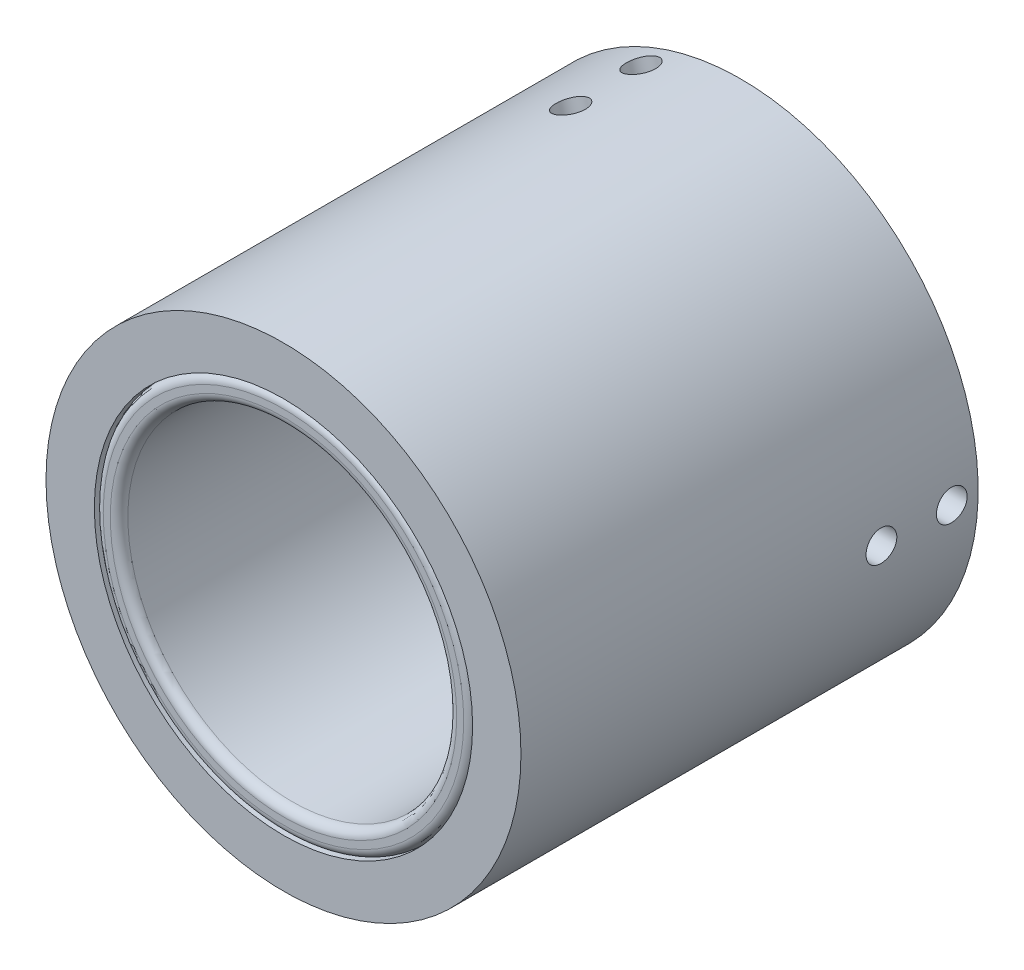
SolidWorks part; units mm, degrees
ref_plane "Plan de face" through (0, 0, 0) normal (0, 0, 1) x (1, 0, 0)
ref_plane "Plan de dessus" through (0, 0, 0) normal (0, 1, 0) x (1, 0, 0)
ref_plane "Plan de droite" through (0, 0, 0) normal (1, 0, 0) x (0, 0, -1)
sketch "Esquisse6" plane through (0, 0, 0) normal (0, 0, 1) x (1, 0, 0)
  line L0 (0, 0) -> (4.4539, 28.1206) construction
  line L1 (0, 0) -> (12.5667, 24.6635) construction
  line L2 (0, 0) -> (19.5026, 19.5026) construction
  line L3 (9.7608, 19.1566) -> (10.8958, 21.3842)
  line L4 (16.9706, 16.9706) -> (15.2028, 15.2028)
  line L5 (19.1566, 9.7608) -> (21.3842, 10.8958)
  line L6 (23.7045, 3.7544) -> (21.2353, 3.3633)
  line L7 (21.2353, -3.3633) -> (23.7045, -3.7544)
  line L8 (21.3842, -10.8958) -> (19.1566, -9.7608)
  line L9 (15.2028, -15.2028) -> (16.9706, -16.9706)
  line L10 (10.8958, -21.3842) -> (9.7608, -19.1566)
  line L11 (3.3633, -21.2353) -> (3.7544, -23.7045)
  line L12 (-3.7544, -23.7045) -> (-3.3633, -21.2353)
  line L13 (-9.7608, -19.1566) -> (-10.8958, -21.3842)
  line L14 (-16.9706, -16.9706) -> (-15.2028, -15.2028)
  line L15 (-19.1566, -9.7608) -> (-21.3842, -10.8958)
  line L16 (-23.7045, -3.7544) -> (-21.2353, -3.3633)
  line L17 (-21.2353, 3.3633) -> (-23.7045, 3.7544)
  line L18 (-21.3842, 10.8958) -> (-19.1566, 9.7608)
  line L19 (-15.2028, 15.2028) -> (-16.9706, 16.9706)
  line L20 (-10.8958, 21.3842) -> (-9.7608, 19.1566)
  line L21 (-3.3633, 21.2353) -> (-3.7544, 23.7045)
  line L22 (3.7544, 23.7045) -> (3.3633, 21.2353)
  line L23 (-10.8958, 21.3842) -> (10.8958, -21.3842) construction
  line L24 (0, 0) -> (0, 33.4225) construction
  line L25 (21.3842, 10.8958) -> (-21.3842, -10.8958) construction
  line L26 (23.7045, 3.7544) -> (-23.7045, -3.7544) construction
  line L27 (23.7045, -3.7544) -> (-23.7045, 3.7544) construction
  line L28 (21.3842, -10.8958) -> (-21.3842, 10.8958) construction
  line L29 (16.9706, -16.9706) -> (-16.9706, 16.9706) construction
  line L30 (3.7544, -23.7045) -> (-3.7544, 23.7045) construction
  line L31 (-3.7544, -23.7045) -> (0, 0) construction
  line L32 (-10.8958, -21.3842) -> (0, 0) construction
  line L33 (-16.9706, -16.9706) -> (0, 0) construction
  circle A0 centre (0, 0) radius 25 construction
  circle A1 centre (0, 0) radius 24 construction
  circle A2 centre (0, 0) radius 21.5 construction
  arc A3 (3.3633, 21.2353) -> (9.7608, 19.1566) centre (0, 0) cw
  arc A4 (10.8958, 21.3842) -> (16.9706, 16.9706) centre (0, 0) cw
  arc A5 (15.2028, 15.2028) -> (19.1566, 9.7608) centre (0, 0) cw
  arc A6 (21.3842, 10.8958) -> (23.7045, 3.7544) centre (0, 0) cw
  arc A7 (21.2353, 3.3633) -> (21.2353, -3.3633) centre (0, 0) cw
  arc A8 (23.7045, -3.7544) -> (21.3842, -10.8958) centre (0, 0) cw
  arc A9 (19.1566, -9.7608) -> (15.2028, -15.2028) centre (0, 0) cw
  arc A10 (16.9706, -16.9706) -> (10.8958, -21.3842) centre (0, 0) cw
  arc A11 (9.7608, -19.1566) -> (3.3633, -21.2353) centre (0, 0) cw
  arc A12 (3.7544, -23.7045) -> (-3.7544, -23.7045) centre (0, 0) cw
  arc A13 (-3.3633, -21.2353) -> (-9.7608, -19.1566) centre (0, 0) cw
  arc A14 (-10.8958, -21.3842) -> (-16.9706, -16.9706) centre (0, 0) cw
  arc A15 (-15.2028, -15.2028) -> (-19.1566, -9.7608) centre (0, 0) cw
  arc A16 (-21.3842, -10.8958) -> (-23.7045, -3.7544) centre (0, 0) cw
  arc A17 (-21.2353, -3.3633) -> (-21.2353, 3.3633) centre (0, 0) cw
  arc A18 (-23.7045, 3.7544) -> (-21.3842, 10.8958) centre (0, 0) cw
  arc A19 (-19.1566, 9.7608) -> (-15.2028, 15.2028) centre (0, 0) cw
  arc A20 (-16.9706, 16.9706) -> (-10.8958, 21.3842) centre (0, 0) cw
  arc A21 (-9.7608, 19.1566) -> (-3.3633, 21.2353) centre (0, 0) cw
  arc A22 (-3.7544, 23.7045) -> (3.7544, 23.7045) centre (0, 0) cw
  circle A23 centre (0, 0) radius 3.025
  circle A24 centre (0, 0) radius 9.025 construction
  circle A25 centre (0, 0) radius 17.5 construction
  point P62 (0, 0)
  dimension "D1" = 50
  dimension "D4" = 2.5
  dimension "D5" = 48
  dimension "D7" = 6.05
  dimension "D9" = 6
  dimension "D10" = 4
  dimension "D2" = 18
  dimension "D3" = 18
  dimension "D8" = 9
  dimension "D6" = 10
extrude "Jante" add sketch "Esquisse6" along normal blind 46 from offset 20
sketch "Esquisse8" plane through (0, 0, 66) normal (0, 0, 1) x (1, 0, 0)
  circle A0 centre (0, 0) radius 21.5
  circle A1 centre (0, 0) radius 3.025
  circle A2 centre (0, 0) radius 3.025 construction
  arc A3 (-15.2028, 15.2028) -> (-19.1566, 9.7608) centre (0, 0) ccw construction
extrude "Boss.-Extru.5" add sketch "Esquisse8" along normal blind 3
sketch "Esquisse9" plane through (0, 0, 20) normal (0, 0, -1) x (-1, 0, 0)
  circle A0 centre (0, 0) radius 21.5
  circle A1 centre (0, 0) radius 3.025
  arc A2 (19.1566, 9.7608) -> (15.2028, 15.2028) centre (0, 0) ccw construction
  circle A3 centre (0, 0) radius 3.025 construction
extrude "Boss.-Extru.6" add sketch "Esquisse9" along normal blind 3
sketch "Esquisse7" plane through (0, 0, 0) normal (0, 0, 1) x (1, 0, 0)
  line L40 (-9.7564, 19.1701) -> (-10.8914, 21.3976)
  line L41 (-16.9847, 16.9706) -> (-15.2169, 15.2028)
  line L42 (-19.161, 9.7742) -> (-21.3885, 10.9092)
  line L43 (-23.716, 3.7461) -> (-21.2467, 3.355)
  line L44 (-21.2467, -3.355) -> (-23.716, -3.7461)
  line L45 (-21.3885, -10.9092) -> (-19.161, -9.7742)
  line L46 (-15.2169, -15.2028) -> (-16.9847, -16.9706)
  line L47 (-10.8914, -21.3976) -> (-9.7564, -19.1701)
  line L48 (-3.3748, -21.2436) -> (-3.7659, -23.7128)
  line L49 (3.7659, -23.7128) -> (3.3748, -21.2436)
  line L50 (9.7564, -19.1701) -> (10.8914, -21.3976)
  line L51 (16.9847, -16.9706) -> (15.2169, -15.2028)
  line L52 (19.161, -9.7742) -> (21.3885, -10.9092)
  line L53 (23.716, -3.7461) -> (21.2467, -3.355)
  line L54 (21.2467, 3.355) -> (23.716, 3.7461)
  line L55 (21.3885, 10.9092) -> (19.161, 9.7742)
  line L56 (15.2169, 15.2028) -> (16.9847, 16.9706)
  line L57 (10.8914, 21.3976) -> (9.7564, 19.1701)
  line L58 (3.3748, 21.2436) -> (3.7659, 23.7128)
  line L59 (-3.7659, 23.7128) -> (-3.3748, 21.2436)
  line L60 (-9.7564, 19.1701) -> (-10.8914, 21.3976)
  line L61 (-16.9847, 16.9706) -> (-15.2169, 15.2028)
  line L62 (-19.161, 9.7742) -> (-21.3885, 10.9092)
  line L63 (-23.716, 3.7461) -> (-21.2467, 3.355)
  line L64 (-21.2467, -3.355) -> (-23.716, -3.7461)
  line L65 (-21.3885, -10.9092) -> (-19.161, -9.7742)
  line L66 (-15.2169, -15.2028) -> (-16.9847, -16.9706)
  line L67 (-10.8914, -21.3976) -> (-9.7564, -19.1701)
  line L68 (-3.3748, -21.2436) -> (-3.7659, -23.7128)
  line L69 (3.7659, -23.7128) -> (3.3748, -21.2436)
  line L70 (9.7564, -19.1701) -> (10.8914, -21.3976)
  line L71 (16.9847, -16.9706) -> (15.2169, -15.2028)
  line L72 (19.161, -9.7742) -> (21.3885, -10.9092)
  line L73 (23.716, -3.7461) -> (21.2467, -3.355)
  line L74 (21.2467, 3.355) -> (23.716, 3.7461)
  line L75 (21.3885, 10.9092) -> (19.161, 9.7742)
  line L76 (15.2169, 15.2028) -> (16.9847, 16.9706)
  line L77 (10.8914, 21.3976) -> (9.7564, 19.1701)
  line L78 (3.3748, 21.2436) -> (3.7659, 23.7128)
  line L79 (-3.7659, 23.7128) -> (-3.3748, 21.2436)
  circle A20 centre (0, 0) radius 27.01
  arc A40 (-3.3748, 21.2436) -> (-9.7564, 19.1701) centre (0, 0) ccw
  arc A41 (-10.8914, 21.3976) -> (-16.9847, 16.9706) centre (0, 0) ccw
  arc A42 (-15.2169, 15.2028) -> (-19.161, 9.7742) centre (0, 0) ccw
  arc A43 (-21.3885, 10.9092) -> (-23.716, 3.7461) centre (0, 0) ccw
  arc A44 (-21.2467, 3.355) -> (-21.2467, -3.355) centre (0, 0) ccw
  arc A45 (-23.716, -3.7461) -> (-21.3885, -10.9092) centre (0, 0) ccw
  arc A46 (-19.161, -9.7742) -> (-15.2169, -15.2028) centre (0, 0) ccw
  arc A47 (-16.9847, -16.9706) -> (-10.8914, -21.3976) centre (0, 0) ccw
  arc A48 (-9.7564, -19.1701) -> (-3.3748, -21.2436) centre (0, 0) ccw
  arc A49 (-3.7659, -23.7128) -> (3.7659, -23.7128) centre (0, 0) ccw
  arc A50 (3.3748, -21.2436) -> (9.7564, -19.1701) centre (0, 0) ccw
  arc A51 (10.8914, -21.3976) -> (16.9847, -16.9706) centre (0, 0) ccw
  arc A52 (15.2169, -15.2028) -> (19.161, -9.7742) centre (0, 0) ccw
  arc A53 (21.3885, -10.9092) -> (23.716, -3.7461) centre (0, 0) ccw
  arc A54 (21.2467, -3.355) -> (21.2467, 3.355) centre (0, 0) ccw
  arc A55 (23.716, 3.7461) -> (21.3885, 10.9092) centre (0, 0) ccw
  arc A56 (19.161, 9.7742) -> (15.2169, 15.2028) centre (0, 0) ccw
  arc A57 (16.9847, 16.9706) -> (10.8914, 21.3976) centre (0, 0) ccw
  arc A58 (9.7564, 19.1701) -> (3.3748, 21.2436) centre (0, 0) ccw
  arc A59 (3.7659, 23.7128) -> (-3.7659, 23.7128) centre (0, 0) ccw
  arc A60 (-3.3748, 21.2436) -> (-9.7564, 19.1701) centre (0, 0) ccw
  arc A61 (-10.8914, 21.3976) -> (-16.9847, 16.9706) centre (0, 0) ccw
  arc A62 (-15.2169, 15.2028) -> (-19.161, 9.7742) centre (0, 0) ccw
  arc A63 (-21.3885, 10.9092) -> (-23.716, 3.7461) centre (0, 0) ccw
  arc A64 (-21.2467, 3.355) -> (-21.2467, -3.355) centre (0, 0) ccw
  arc A65 (-23.716, -3.7461) -> (-21.3885, -10.9092) centre (0, 0) ccw
  arc A66 (-19.161, -9.7742) -> (-15.2169, -15.2028) centre (0, 0) ccw
  arc A67 (-16.9847, -16.9706) -> (-10.8914, -21.3976) centre (0, 0) ccw
  arc A68 (-9.7564, -19.1701) -> (-3.3748, -21.2436) centre (0, 0) ccw
  arc A69 (-3.7659, -23.7128) -> (3.7659, -23.7128) centre (0, 0) ccw
  arc A70 (3.3748, -21.2436) -> (9.7564, -19.1701) centre (0, 0) ccw
  arc A71 (10.8914, -21.3976) -> (16.9847, -16.9706) centre (0, 0) ccw
  arc A72 (15.2169, -15.2028) -> (19.161, -9.7742) centre (0, 0) ccw
  arc A73 (21.3885, -10.9092) -> (23.716, -3.7461) centre (0, 0) ccw
  arc A74 (21.2467, -3.355) -> (21.2467, 3.355) centre (0, 0) ccw
  arc A75 (23.716, 3.7461) -> (21.3885, 10.9092) centre (0, 0) ccw
  arc A76 (19.161, 9.7742) -> (15.2169, 15.2028) centre (0, 0) ccw
  arc A77 (16.9847, 16.9706) -> (10.8914, 21.3976) centre (0, 0) ccw
  arc A78 (9.7564, 19.1701) -> (3.3748, 21.2436) centre (0, 0) ccw
  arc A79 (3.7659, 23.7128) -> (-3.7659, 23.7128) centre (0, 0) ccw
  dimension "D2" = 3
  dimension "D1" = 0.01
extrude "Pneu" add sketch "Esquisse7" along normal up to surface (66 mm away) from offset 20 separate body up to face at (-13.2898, 18.2918, 66)
sketch "Esquisse10" plane through (0, 0, 66) normal (0, 0, 1) x (1, 0, 0)
  circle A1 centre (0, 0) radius 27.01
  circle A3 centre (0, 0) radius 21.51
  circle A4 centre (0, 0) radius 27.01 construction
  arc A5 (-9.7564, -19.1701) -> (-3.3748, -21.2436) centre (0, 0) ccw construction
extrude "Boss.-Extru.7" add sketch "Esquisse10" along normal blind 3
sketch "Esquisse11" plane through (0, 0, 20) normal (0, 0, -1) x (-1, 0, 0)
  circle A0 centre (0, 0) radius 21.51
  circle A1 centre (0, 0) radius 27.01
  circle A2 centre (0, 0) radius 27.01 construction
  arc A3 (19.161, 9.7742) -> (15.2169, 15.2028) centre (0, 0) ccw construction
extrude "Boss.-Extru.8" add sketch "Esquisse11" along normal blind 3
sketch "Esquisse15" plane through (0, 0, 17) normal (0, 0, -1) x (-1, 0, 0)
  line L0 (0, 0) -> (26.1385, -8.4929) construction
  line L1 (42.5408, 0) -> (0, 0) construction
  dimension "D1" = 18
ref_plane "Plan1" through (0, 0, 0) normal (0.309, -0.9511, 0) x (-0.9511, -0.309, 0)
sketch "Esquisse5" plane through (0, 0, 0) normal (0.309, -0.9511, 0) x (0, 0, -1)
  line L0 (-17, -27.01) -> (-17, 27.01) construction
  circle A0 centre (4, 0) radius 1.75
  circle A1 centre (-20, 0) radius 1.75
  circle A2 centre (-28, 0) radius 1.75
  dimension "D2" = 3.5
  dimension "D5" = 3.5
  dimension "D6" = 3.5
  dimension "D1" = 4
  dimension "D3" = 3
  dimension "D4" = 8
extrude "Enlèv. mat.-Extru.2" cut sketch "Esquisse5" against normal through all and the other way through all
sketch "Esquisse4" plane through (0, 0, 0) normal (1, 0, 0) x (0, -1, 0)
  line L1 (27.01, -17) -> (-27.01, -17) construction
  circle A0 centre (0, 4) radius 1.75
  circle A1 centre (0, -20) radius 1.75
  circle A2 centre (0, -28) radius 1.75
  dimension "D2" = 3.5
  dimension "D6" = 3.5
  dimension "D1" = 4
  dimension "D3" = 8
  dimension "D5" = 3
extrude "Enlèv. mat.-Extru.1" cut sketch "Esquisse4" against normal through all and the other way through all
sketch "Esquisse12" plane through (0, 0, 69) normal (0, 0, 1) x (1, 0, 0)
  line L0 (-6.3816, 6.3816) -> (-7.9448, 15.5926)
  line L3 (4.0973, 8.0413) -> (12.3744, 12.3744)
  line L5 (-17.2845, 2.7376) -> (-8.0413, 4.0973)
  line L7 (-8.0413, 4.0973) -> (-6.3816, 6.3816)
  line L8 (-2.7376, 17.2845) -> (1.4118, 8.9139)
  line L9 (1.4118, 8.9139) -> (4.0973, 8.0413)
  line L10 (8.9139, -1.4118) -> (15.5926, -7.9448)
  line L11 (15.5926, 7.9448) -> (8.9139, 1.4118)
  line L12 (8.9139, 1.4118) -> (8.9139, -1.4118)
  line L13 (1.4118, -8.9139) -> (-2.7376, -17.2845)
  line L14 (12.3744, -12.3744) -> (4.0973, -8.0413)
  line L15 (4.0973, -8.0413) -> (1.4118, -8.9139)
  line L16 (-8.0413, -4.0973) -> (-17.2845, -2.7376)
  line L17 (-7.9448, -15.5926) -> (-6.3816, -6.3816)
  line L18 (-6.3816, -6.3816) -> (-8.0413, -4.0973)
  line L19 (21.3842, -10.8958) -> (-21.3842, 10.8958) construction
  line L20 (16.9706, -16.9706) -> (-16.9706, 16.9706) construction
  line L21 (23.7045, -3.7544) -> (-23.7045, 3.7544) construction
  line L22 (-10.8958, 21.3842) -> (10.8958, -21.3842) construction
  circle A0 centre (0, 0) radius 9.025 construction
  circle A1 centre (0, 0) radius 17.5 construction
  arc A4 (-17.2845, 2.7376) -> (-7.9448, 15.5926) centre (0, 0) cw
  arc A5 (-2.7376, 17.2845) -> (12.3744, 12.3744) centre (0, 0) cw
  arc A6 (15.5926, 7.9448) -> (15.5926, -7.9448) centre (0, 0) cw
  arc A7 (12.3744, -12.3744) -> (-2.7376, -17.2845) centre (0, 0) cw
  arc A8 (-7.9448, -15.5926) -> (-17.2845, -2.7376) centre (0, 0) cw
  point P36 (0, 0)
  dimension "D1" = 5
extrude "Enlèv. mat.-Extru.7" cut sketch "Esquisse12" against normal through all
sketch "Esquisse13" plane through (0, 0, 69) normal (0, 0, -1) x (-1, 0, 0)
  circle A0 centre (0, 0) radius 18.7
  dimension "D1" = 37.4
extrude "Enlèv. mat.-Extru.9" cut sketch "Esquisse13" along normal offset from surface (37.2 mm away) 14.8 up to face at (-10.2989, -7.4826, 17)
sketch "Esquisse14" plane through (0, 0, 17) normal (0, 0, -1) x (-1, 0, 0)
  circle A0 centre (0, 0) radius 21.5
  circle A1 centre (0, 0) radius 34.9398
extrude "Enlèv. mat.-Extru.10" cut sketch "Esquisse14" against normal blind 22 from offset 15 offset against normal yes
fillet "Congé1" radius 1 104 edges at (21.5, 0, 69) (-18.7, 0, 69) (-3.025, 0, 17) (-21.5, 0, 17) (-12.6629, 3.4174, 17) (-14.1578, 10.2862, 17) (-7.1632, 10.9871, 17) (-7.2115, 5.2395, 17) (-0.6629, 13.0992, 17) (5.4078, 16.6435, 17) (8.2358, 10.2079, 17) (2.7545, 8.4776, 17) (12.2533, 4.6783, 17) (17.5, 0, 17) (12.2533, -4.6783, 17) (8.9139, 0, 17) (8.2358, -10.2079, 17) (5.4078, -16.6435, 17) (-0.6629, -13.0992, 17) (2.7545, -8.4776, 17) (-7.1632, -10.9871, 17) (-14.1578, -10.2862, 17) (-12.6629, -3.4174, 17) (-7.2115, -5.2395, 17) (21.3842, -10.8958, 60) (21.3842, -10.8958, 26) (22.8254, -7.4164, 66) (23.7045, -3.7544, 60) (23.7045, -3.7544, 26) (22.8254, -7.4164, 20) (10.8958, -21.3842, 60) (10.8958, -21.3842, 26) (14.1068, -19.4164, 66) (16.9706, -16.9706, 60) (16.9706, -16.9706, 26) (14.1068, -19.4164, 20) (-3.7544, -23.7045, 60) (-3.7544, -23.7045, 26) (0, -24, 66) (3.7544, -23.7045, 60) (3.7544, -23.7045, 26) (0, -24, 20) (-16.9706, -16.9706, 60) (-16.9706, -16.9706, 26) (-14.1068, -19.4164, 66) (-10.8958, -21.3842, 60) (-10.8958, -21.3842, 26) (-14.1068, -19.4164, 20) (-23.7045, -3.7544, 60) (-23.7045, -3.7544, 26) (-22.8254, -7.4164, 66) (-21.3842, -10.8958, 60) (-21.3842, -10.8958, 26) (-22.8254, -7.4164, 20) (-21.3842, 10.8958, 60) (-21.3842, 10.8958, 26) (-22.8254, 7.4164, 66) (-23.7045, 3.7544, 60) (-23.7045, 3.7544, 26) (-22.8254, 7.4164, 20) (23.7045, 3.7544, 60) (23.7045, 3.7544, 26) (22.8254, 7.4164, 66) (21.3842, 10.8958, 60) (21.3842, 10.8958, 26) (22.8254, 7.4164, 20) (16.9706, 16.9706, 60) (16.9706, 16.9706, 26) (14.1068, 19.4164, 66) (10.8958, 21.3842, 60) (10.8958, 21.3842, 26) (14.1068, 19.4164, 20) (3.7544, 23.7045, 60) (3.7544, 23.7045, 26) (0, 24, 66) (-3.7544, 23.7045, 60) (-3.7544, 23.7045, 26) (0, 24, 20) (-10.8958, 21.3842, 60) (-10.8958, 21.3842, 26) (-14.1068, 19.4164, 66) (-16.9706, 16.9706, 60) (-16.9706, 16.9706, 26) (-14.1068, 19.4164, 20) (0, -24, 32) (0, 24, 32) (22.8254, 7.4164, 32) (22.8254, -7.4164, 32) (14.1068, -19.4164, 32) (-14.1068, -19.4164, 32) (-22.8254, -7.4164, 32) (-14.1068, 19.4164, 54) (-22.8254, 7.4164, 54) (-22.8254, -7.4164, 54) (-14.1068, -19.4164, 54) (0, -24, 54) (22.8254, 7.4164, 54) (14.1068, -19.4164, 54) (22.8254, -7.4164, 54) (0, 24, 54) (14.1068, 19.4164, 54) (14.1068, 19.4164, 32) (-22.8254, 7.4164, 32) (-14.1068, 19.4164, 32)
